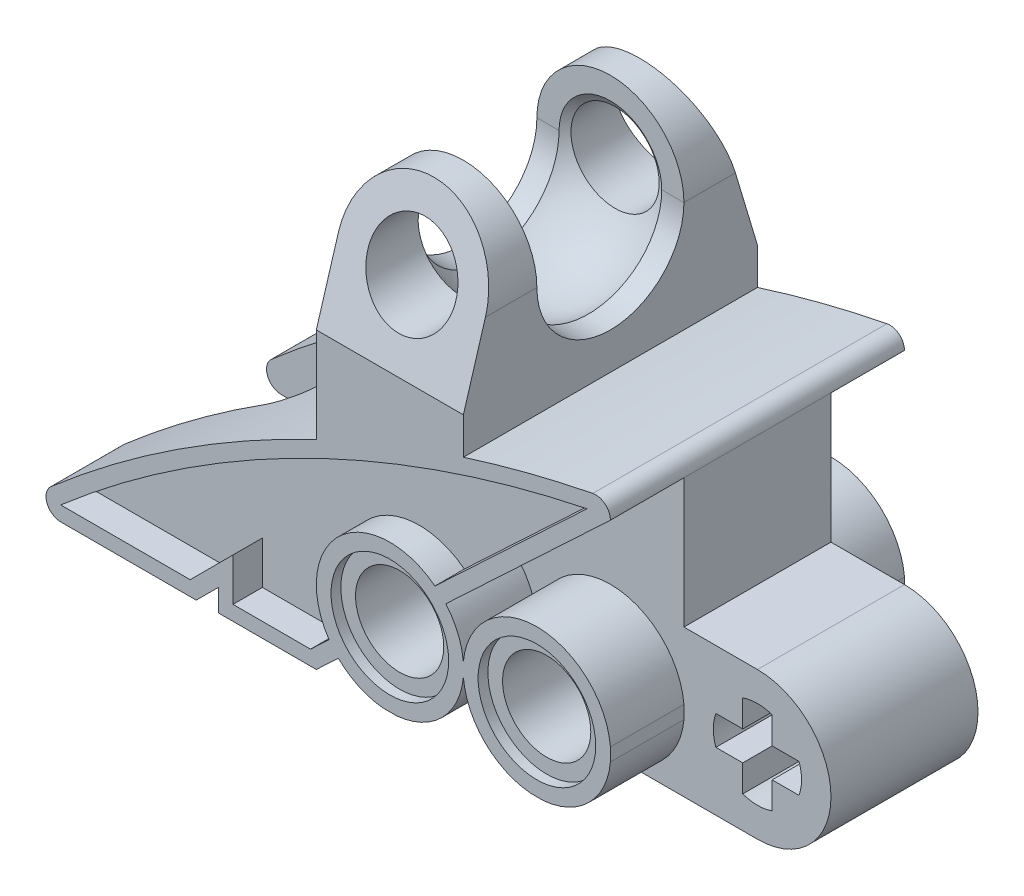
SolidWorks part; units mm, degrees
ref_plane "Front Plane" through (0, 0, 0) normal (0, 0, 1) x (1, 0, 0)
ref_plane "Top Plane" through (0, 0, 0) normal (0, 1, 0) x (1, 0, 0)
ref_plane "Right Plane" through (0, 0, 0) normal (1, 0, 0) x (0, 0, -1)
sketch "Sketch1" plane through (0, 0, 0) normal (0, 1, 0) x (1, 0, 0)
  line L0 (-3.3333, 1.5) -> (-3.3333, -1.5)
  line L1 (-10, -5) -> (10, -5)
  line L2 (-10, -5) -> (-10, 5)
  line L3 (-10, 5) -> (10, 5)
  line L4 (10, -5) -> (10, 5)
  line L5 (-10, -5) -> (10, 5) construction
  line L6 (-10, 5) -> (10, -5) construction
  line L7 (-4.3333, -2.5) -> (-10, -2.5)
  line L8 (10, -2.5) -> (10, 2.5)
  line L9 (-4.3333, 2.5) -> (-10, 2.5)
  line L10 (-10, -2.5) -> (-10, 2.5)
  line L11 (10, -2.5) -> (-10, 2.5) construction
  line L12 (10, 2.5) -> (-10, -2.5) construction
  arc A0 (-3.3333, 1.5) -> (-4.3333, 2.5) centre (-4.3333, 1.5) ccw
  arc A1 (-3.3333, -1.5) -> (-4.3333, -2.5) centre (-4.3333, -1.5) cw
  point P0 (0, 0)
  point P6 (0, 0)
  dimension "D5" = 1
  dimension "D4" = 1
  dimension "D1" = 10
  dimension "D2" = 20
  dimension "D3" = 2.5
  dimension "D6" = 6.6667
extrude "Boss-Extrude1" add sketch "Sketch1" along normal blind 10 contours L0 A1 L7 L2 L1 L4 L3 L9 A0 | A1 L0 A0 L9 L2 L7 region at (1.3208, 0, 0) region at (-6.7072, 0, 0)
sketch "Sketch2" plane through (0, 10, 0) normal (0, 1, 0) x (1, 0, 0)
  line L1 (-10, -5) -> (10, -5)
  line L2 (-10, -5) -> (-10, 5)
  line L3 (-10, 5) -> (10, 5)
  line L4 (10, -5) -> (10, 5)
  line L5 (0, 5) -> (10, 5)
  line L6 (0, 5) -> (0, -5)
  line L7 (0, -5) -> (10, -5)
  line L8 (10, 5) -> (10, -5)
  line L9 (0, 5) -> (5, 5)
  line L10 (0, 5) -> (0, -5)
  line L11 (0, -5) -> (5, -5)
  line L12 (5, 5) -> (5, -5)
extrude "Boss-Extrude3" add sketch "Sketch2" along normal blind 5 contours L12 L5 L6 L1 region at (2.5, 10, 0)
sketch "Sketch4" plane through (10, 0, 0) normal (1, 0, 0) x (0, 0, -1)
  line L0 (-5, 0) -> (5, 0) construction
  line L1 (-2.5, 0) -> (2.5, 0)
  line L2 (-2.5, 0) -> (-2.5, 5)
  line L3 (-2.5, 5) -> (2.5, 5)
  line L4 (2.5, 0) -> (2.5, 5)
  line L5 (5, 0) -> (-5, 0)
  point P10 (0, 0)
  line M4 (-5, 0) -> (5, 0)
  dimension "D1" = 5
extrude "Boss-Extrude4" add sketch "Sketch4" along normal blind 5 contours L4 L3 L2 M4 region at (10, 2.5, 0)
sketch "Sketch5" plane through (0, 0, 5) normal (0, 0, 1) x (1, 0, 0)
  line L0 (1, 12.5) -> (2.5, 12.5)
  line L1 (2.5, 12.5) -> (2.5, 11)
  circle A0 centre (2.5, 12.5) radius 2.5
  circle A1 centre (2.5, 12.5) radius 1.5
  line M5 (5, 10) -> (5, 15)
  line M6 (5, 15) -> (0, 15)
  line M7 (0, 15) -> (0, 10)
  dimension "D1" = 3
sketch "Sketch6" plane through (5, 0, 0) normal (1, 0, 0) x (0, 0, -1)
  line L0 (-5, 10) -> (-3.5, 15)
  line L1 (5, 15) -> (-5, 15) construction
  line L2 (-3.5, 15) -> (-5, 15)
  line L3 (-5, 15) -> (-5, 10)
  line L4 (5, 10) -> (3.5, 15)
  line L5 (3.5, 15) -> (5, 15)
  line L6 (5, 15) -> (5, 10)
  dimension "D1" = 1.5
extrude "Cut-Extrude2" cut sketch "Sketch6" against normal blind 5
extrude "Cut-Extrude3" cut sketch "Sketch5" against normal blind 10 contours L1 A1 L0 | A0 M5 M6 | A0 M6 M7 region at (2.7122, 12.7122, 5) region at (4.4416, 14.4416, 5) region at (0.5584, 14.4416, 5)
sketch "Sketch7" plane through (0, 12.5, 0) normal (0, 1, 0) x (1, 0, 0)
  line L1 (2.5, 4.25) -> (2.5, -4.25) construction
  line L2 (2.5, 4.25) -> (2.5, -4.2104)
  arc A0 (2.5, -2.9397) -> (2.5, 3.0603) centre (2.5, 0.0603) ccw
  dimension "D1" = 6
revolve "Cut-Revolve1" cut sketch "Sketch7" angle 360 about L2 region at (3.7732, 12.5, -0.0603)
sketch "Sketch8" plane through (5, 0, 0) normal (1, 0, 0) x (0, 0, -1)
  line L0 (-4.25, 12.5) -> (4.25, 12.5)
  line L1 (-2.5, 12.5) -> (2.5, 12.5)
  line L2 (2.5, 12.5) -> (2.5, 15)
  line L3 (2.5, 15) -> (-2.5, 15)
  line L4 (-2.5, 15) -> (-2.5, 12.5)
  circle A0 centre (0, 12.5) radius 2.5
  dimension "D1" = 5
extrude "Cut-Extrude4" cut sketch "Sketch8" against normal blind 10
extrude "Cut-Extrude5" cut sketch "Sketch5<4>" against normal blind 10 contours L0 A1 L1 region at (1.8634, 11.8634, 5)
sketch "Sketch5<4>" plane through (0, 0, 5) normal (0, 0, 1) x (1, 0, 0) same geometry as "Sketch5"
sketch "Sketch9" plane through (0, 0, 2.5) normal (0, 0, 1) x (1, 0, 0)
  line L1 (11, 2) -> (14, 2)
  line L2 (11, 2) -> (11, 3)
  line L3 (11, 3) -> (14, 3)
  line L4 (14, 2) -> (14, 3)
  line L5 (11, 2) -> (14, 3) construction
  line L6 (11, 3) -> (14, 2) construction
  line L7 (12, 1) -> (13, 1)
  line L8 (12, 1) -> (12, 4)
  line L9 (12, 4) -> (13, 4)
  line L10 (13, 1) -> (13, 4)
  line L11 (12, 1) -> (13, 4) construction
  line L12 (12, 4) -> (13, 1) construction
  line L13 (10, 5) -> (15, 5)
  line L14 (10, 5) -> (10, 0)
  line L15 (10, 0) -> (15, 0)
  line L16 (15, 5) -> (15, 0)
  circle A0 centre (12.5, 2.5) radius 2.5
  circle A1 centre (12.5, 2.5) radius 1.5
  point P18 (15, 2.5)
  point P20 (12.5, 5)
  line M3 (15, 0) -> (15, 5)
  line M4 (15, 5) -> (10, 5)
  dimension "D1" = 3
  dimension "D2" = 3
  dimension "D3" = 1
extrude "Cut-Extrude7" cut sketch "Sketch9" against normal blind 5 contours A0 L16 M4 | A0 L15 M3 | A1 L3 L10 L1 | L10 A1 L8 L3 | L1 L10 L3 L8 | L3 A1 L1 L8 | L8 A1 L10 L1 region at (11.5138, 2.5, 2.5) region at (12.5, 2.5, 2.5) region at (12.5, 1.5138, 2.5) region at (13.4862, 2.5, 2.5) region at (12.5, 3.4862, 2.5) region at (14.4416, 4.4416, 2.5) region at (14.4416, 0.5584, 2.5)
sketch "Sketch10" plane through (0, 0, 5) normal (0, 0, 1) x (1, 0, 0)
  line L0 (0, 0) -> (0, 10)
  line L1 (-10, 0) -> (10, 0) construction
  line L2 (5, 10) -> (5, 8.7508)
  line L3 (0, 10) -> (-10, 10)
  line L4 (-10, 10) -> (-10, 0)
  line L5 (-3.3333, 10) -> (-3.3333, 4.991)
  line L6 (-3.3333, 4.991) -> (0, 10)
  arc A0 (-10, 0) -> (10, 10) centre (17.1756, -29.3511) cw
  line M1 (10, 10) -> (5, 10)
  line M3 (0, 10) -> (-10, 10)
  line M4 (-10, 10) -> (-10, 0)
  dimension "D2" = 3.3333
  dimension "D1" = 40
extrude "Cut-Extrude8" cut sketch "Sketch10" against normal blind 10 contours A0 L5 L3 M4 | L5 L6 M3 | L2 A0 M1 region at (6.5836, 9.6013, 5) region at (-2.2222, 8.3303, 5) region at (-7.044, 6.1971, 5)
extrude "Cut-Extrude9" cut sketch "Sketch10<3>" against normal blind 3.3333 contours L6 A0 L0 region at (-1.099, 7.2839, 5)
sketch "Sketch10<3>" plane through (0, 0, 5) normal (0, 0, 1) x (1, 0, 0) same geometry as "Sketch10"
sketch "Sketch13" plane through (0, 0, -5) normal (0, 0, -1) x (-1, 0, 0)
  line L0 (0, 10) -> (0, 0)
  line L1 (10, 0) -> (-10, 0) construction
  line L2 (0, 10) -> (3.3333, 4.991)
  arc A0 (-10, 10) -> (10, 0) centre (-17.1756, -29.3511) cw
  line M6 (3.3333, 4.991) -> (0, 10)
extrude "Cut-Extrude10" cut sketch "Sketch13" against normal blind 3.3333 contours L0 A0 M6 region at (-1.099, 7.2839, -5)
extrude "Cut-Extrude11" cut sketch "Sketch1<5>" along normal blind 10 contours A1 L0 A0 L9 L2 L7 region at (-6.7072, 0, 0)
sketch "Sketch1<5>" plane through (0, 0, 0) normal (0, 1, 0) x (1, 0, 0) same geometry as "Sketch1"
sketch "Sketch14" plane through (0, 0, 5) normal (0, 0, 1) x (1, 0, 0)
  line L0 (10, 10) -> (10, 0) construction
  line L1 (-10, 0) -> (10, 0) construction
  circle A0 centre (9.5, 9.3959) radius 0.5
  arc A1 (10, 10) -> (5, 8.7508) centre (17.1756, -29.3511) ccw construction
  circle A2 centre (-8.6926, 0.5) radius 0.5
  arc A3 (0, 6.7737) -> (-10, 0) centre (17.1756, -29.3511) ccw construction
  arc M3 (0, 6.7737) -> (-10, 0) centre (17.1756, -29.3511) ccw
  line M4 (-10, 0) -> (10, 0)
  line M5 (10, 0) -> (10, 10)
  arc M6 (10, 10) -> (5, 8.7508) centre (17.1756, -29.3511) ccw
extrude "Cut-Extrude12" cut sketch "Sketch14" against normal blind 10 contours A2 M3 M4 | A0 M5 M6 region at (-9.3995, 0.233, 5) region at (9.8626, 9.8357, 5)
sketch "Sketch15" plane through (0, 0, 5) normal (0, 0, 1) x (1, 0, 0)
  line L2 (0, 0) -> (10, 9.3959)
  line L3 (0, 0) -> (10, 0)
  line L4 (10, 0) -> (10, 9.3959)
  circle A0 centre (7.5, 2.5) radius 2.51
  circle A1 centre (7.5, 2.5) radius 2
  circle A2 centre (7.5, 2.5) radius 1.5
  circle A3 centre (2.5, 2.5) radius 2.51
  circle A4 centre (2.5, 2.5) radius 2
  circle A5 centre (2.5, 2.5) radius 1.5
  line M18 (-8.6926, 0) -> (10, 0)
  line M19 (10, 0) -> (10, 9.3959)
  dimension "D1" = 2.5
  dimension "D2" = 2.5
  dimension "D3" = 3
  dimension "D4" = 4
  dimension "D5" = 2
extrude "Cut-Extrude19" cut sketch "Sketch15" against normal up to surface (2.5 mm away) contours A3 A0 L2 M19 | A0 M18 M19 region at (8.1415, 5.9885, 5) region at (9.4506, 0.5494, 5) up to face at (12.5, 2.5, 2.5)
extrude "Cut-Extrude20" cut sketch "Sketch15<10>" against normal blind 10 contours A3 A0 M18 | A3 L2 M18 | A2 | L2 A5 | L2 A5 region at (0.8846, 0.2177, 5) region at (5, 0.5494, 5) region at (2.1045, 2.9209, 5) region at (2.9769, 1.9924, 5) region at (7.5, 2.5, 5)
sketch "Sketch15<10>" plane through (0, 0, 5) normal (0, 0, 1) x (1, 0, 0) same geometry as "Sketch15"
extrude "Cut-Extrude21" cut sketch "Sketch15<11>" against normal blind 0.3333 contours A1 A2 | A5 L2 A4 | A5 L2 A4 region at (1.1643, 3.9216, 5) region at (1.3349, 1.1895, 5) region at (5.5566, 2.5, 5)
sketch "Sketch15<11>" plane through (0, 0, 5) normal (0, 0, 1) x (1, 0, 0) same geometry as "Sketch15"
sketch "Sketch16" plane through (0, 0, -5) normal (0, 0, -1) x (-1, 0, 0)
  line L0 (0, 0) -> (-10, 9.3959)
  circle A0 centre (-7.5, 2.5) radius 2.51
  circle A1 centre (-2.5, 2.5) radius 2.51
  circle A2 centre (-7.5, 2.5) radius 2
  circle A3 centre (-2.5, 2.5) radius 2
  circle M1 centre (-7.5, 2.5) radius 1.5
  circle M2 centre (-2.5, 2.5) radius 1.5
  line M14 (-10, 9.3959) -> (-10, 0)
  line M15 (-10, 0) -> (-7.2762, 0)
  dimension "D1" = 4
  dimension "D2" = 4
extrude "Cut-Extrude23" cut sketch "Sketch16" against normal up to surface (2.5 mm away) contours A1 L0 A0 M14 | A0 M14 M15 region at (8.1415, 5.9885, -5) region at (9.4506, 0.5494, -5) up to face at (12.5, 2.5, -2.5)
extrude "Cut-Extrude24" cut sketch "Sketch16<4>" against normal blind 0.3333 contours A2 M1 | L0 A3 M2 | L0 A3 M2 region at (3.8372, 1.0768, -5) region at (1.2688, 1.2599, -5) region at (9.4434, 2.5, -5)
sketch "Sketch16<4>" plane through (0, 0, -5) normal (0, 0, -1) x (-1, 0, 0) same geometry as "Sketch16"
sketch "Sketch17" plane through (0, 0, 5) normal (0, 0, 1) x (1, 0, 0)
  line L0 (-4.0833, 0) -> (-8.6926, 0)
  line L1 (-3.3333, 0) -> (-3.3333, 0.75)
  line L2 (-3.3333, 0.75) -> (-3.333, 0)
  line L3 (-3.3333, 0.75) -> (-4.0833, 0)
  line L4 (-3.3333, 0) -> (0, 0)
  line L5 (0, 0) -> (10, 9.3959)
  line L6 (-0.3424, 0.3644) -> (9.6576, 9.7603)
  line L7 (-3.6869, 1.1036) -> (-4.2904, 0.5)
  line L8 (-4.2904, 0.5) -> (-8.6926, 0.5)
  line L9 (-0.198, 0.5) -> (9.6576, 9.7603)
  line L10 (-2.8333, 0.5) -> (-0.198, 0.5)
  line L11 (-2.8333, 0.5) -> (-2.8333, 0.75)
  line L12 (-4.2904, 0.5) -> (-2.8333, 1.9571)
  line L13 (-2.8333, 1.9571) -> (-2.8333, 0.5)
  arc A0 (-9.02, 0.8779) -> (9.4028, 9.8864) centre (17.1756, -29.3511) cw
  arc A1 (-8.6926, 0.5) -> (9.5, 9.3959) centre (17.1756, -29.3511) cw
  circle A4 centre (2.5, 2.5) radius 2.5
  circle A5 centre (2.5, 2.5) radius 2.5
  line M26 (-8.6926, 0) -> (0, 0)
  dimension "D1" = 3.3333
  dimension "D2" = 0.75
  dimension "D3" = 0.75
  dimension "D5" = 0.5
  dimension "D4" = 0.5
  dimension "D6" = 0.5
  dimension "D7" = 0.5
extrude "Cut-Extrude25" cut sketch "Sketch17" against normal blind 1 contours A5 L9 A1 L8 L7 L12 L13 L11 L10 L6 region at (-0.1056, 4.2294, 5)
mirror "Mirror1" about plane through (0, 0, 0) normal (0, 0, 1) of "Cut-Extrude25"
extrude "Cut-Extrude26" cut sketch "Sketch17<3>" against normal blind 10 contours L1 L3 M26 region at (-3.5833, 0.25, 5)
sketch "Sketch17<3>" plane through (0, 0, 5) normal (0, 0, 1) x (1, 0, 0) same geometry as "Sketch17"
equation "\"u\" = 1"
equation "\"sphere\" = 6"
equation "\"D1@Sketch7\"=\"sphere\""
